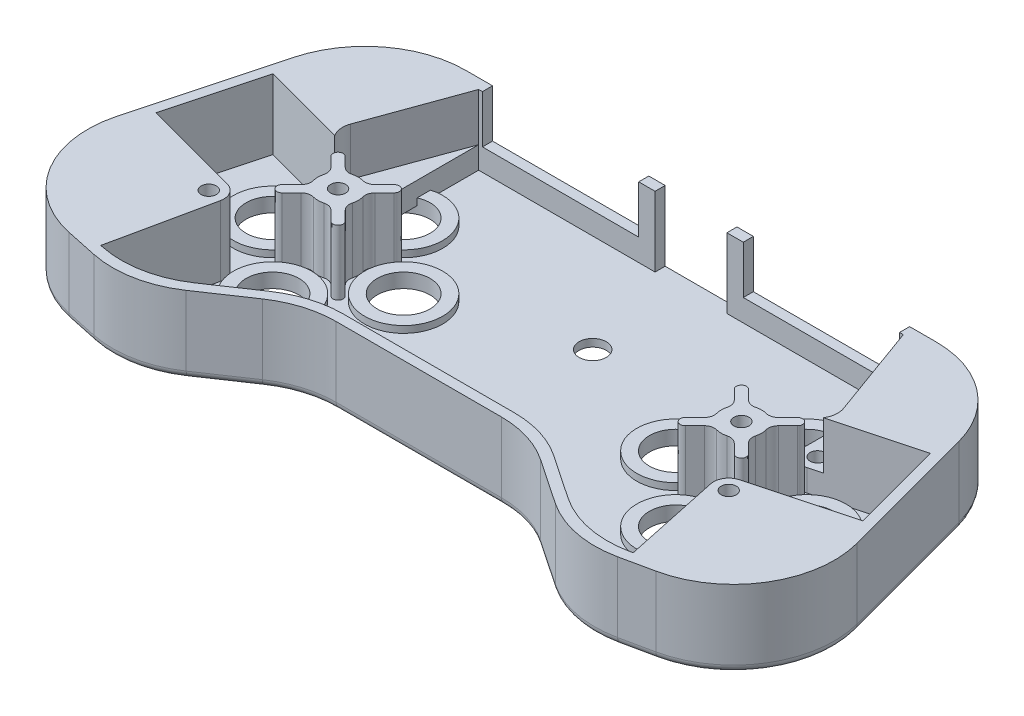
SolidWorks part; units mm, degrees
ref_plane "Front Plane" through (0, 0, 0) normal (0, 0, 1) x (1, 0, 0)
ref_plane "Top Plane" through (0, 0, 0) normal (0, 1, 0) x (1, 0, 0)
ref_plane "Right Plane" through (0, 0, 0) normal (1, 0, 0) x (0, 0, -1)
sketch "Sketch10" plane through (0, 0, 0) normal (0, 1, 0) x (1, 0, 0)
  line L0 (62, 32) -> (-62, 32)
  line L1 (-62, 32) -> (-78.8232, -30.7852)
  line L2 (-78.8232, -30.7852) -> (-43.6451, -38.2625)
  line L3 (-43.6451, -38.2625) -> (-22.5, -24)
  line L4 (-22.5, -24) -> (22.5, -24)
  line L5 (22.5, -24) -> (43.6451, -38.2625)
  line L6 (43.6451, -38.2625) -> (78.8232, -30.7852)
  line L7 (78.8232, -30.7852) -> (62, 32)
  line L8 (40, 13) -> (40, -13) construction
  line L9 (27, 0) -> (53, 0) construction
  line L10 (-40, 13) -> (-40, -13) construction
  line L11 (-53, 0) -> (-27, 0) construction
  line L12 (-27, 0) -> (27, 0) construction
  line L13 (0, 0) -> (0, 32) construction
  line L14 (0, 0) -> (0, -24) construction
  line L15 (78.8232, -30.7852) -> (22.5, -24) construction
  line L16 (-22.5, -24) -> (-78.8232, -30.7852) construction
  circle A0 centre (40, 13) radius 5.25
  circle A1 centre (27, 0) radius 5.25
  circle A2 centre (40, -13) radius 5.25
  circle A3 centre (53, 0) radius 5.25
  circle A4 centre (-40, 13) radius 5.25
  circle A5 centre (-53, 0) radius 5.25
  circle A6 centre (-40, -13) radius 5.25
  circle A7 centre (-27, 0) radius 5.25
  point P16 (40, 0)
  point P17 (-40, 0)
  dimension "D1" = 10.5
  dimension "D2" = 26
  dimension "D3" = 65
  dimension "D4" = 124
  dimension "D5" = 80
  dimension "D6" = 105
  dimension "D7" = 56
  dimension "D8" = 45
  dimension "D9" = 32
  dimension "D10" = 12
  dimension "D11" = 34
extrude "Boss-Extrude5" add sketch "Sketch10" along normal blind 1.5 separate body
sketch "Sketch11" plane through (0, 1.5, 0) normal (0, 1, 0) x (1, 0, 0)
  line L0 (-78.8232, -30.7852) -> (-62, 32)
  line L1 (-62, 32) -> (62, 32)
  line L2 (62, 32) -> (78.8232, -30.7852)
  line L3 (78.8232, -30.7852) -> (43.6451, -38.2625)
  line L4 (43.6451, -38.2625) -> (22.5, -24)
  line L5 (22.5, -24) -> (-22.5, -24)
  line L6 (-22.5, -24) -> (-43.6451, -38.2625)
  line L7 (-43.6451, -38.2625) -> (-78.8232, -30.7852)
  line L8 (-44.0596, -36.1297) -> (-76.3459, -29.2671)
  line L9 (-76.3459, -29.2671) -> (-60.4653, 30)
  line L10 (-60.4653, 30) -> (60.4653, 30)
  line L11 (60.4653, 30) -> (76.3459, -29.2671)
  line L12 (76.3459, -29.2671) -> (44.0596, -36.1297)
  line L13 (44.0596, -36.1297) -> (23.1115, -22)
  line L14 (23.1115, -22) -> (-23.1115, -22)
  line L15 (-23.1115, -22) -> (-44.0596, -36.1297)
  dimension "D1" = 2
extrude "Boss-Extrude7" add sketch "Sketch11" along direction (0, -1, 0) on the side of the normal offset from surface (13.875 mm away) 15.375 up to face at (-40, 0, 18.25)
fillet "Fillet4" radius 20 16 edges at (62, 7.6875, -32) (78.8232, 7.6875, 30.7852) (43.6451, 7.6875, 38.2625) (22.5, 7.6875, 24) (-22.5, 7.6875, 24) (-43.6451, 7.6875, 38.2625) (-62, 7.6875, -32) (-78.8232, 7.6875, 30.7852) (76.3459, 8.4375, 29.2671) (60.4653, 8.4375, -30) (44.0596, 8.4375, 36.1297) (23.1115, 8.4375, 22) (-23.1115, 8.4375, 22) (-44.0596, 8.4375, 36.1297) (-76.3459, 8.4375, 29.2671) (-60.4653, 8.4375, -30)
fillet "Fillet5" radius 1.5 16 edges at (43.9746, 0, 36.5671) (32.0881, 0, 30.4673) (22.2328, 0, 24.8739) (0, 0, 24) (-22.2328, 0, 24.8739) (-32.0881, 0, 30.4673) (-43.9746, 0, 36.5671) (-55.0786, 0, 35.8323) (-71.1028, 0, 26.0541) (-69.6702, 0, -3.3743) (-58.8287, 0, -27.8671) (0, 0, -32) (58.8287, 0, -27.8671) (69.6702, 0, -3.3743) (71.1028, 0, 26.0541) (55.0786, 0, 35.8323)
sketch "Sketch12" plane through (0, 1.5, 0) normal (0, 1, 0) x (1, 0, 0)
  line L0 (-65.2138, 12.2786) -> (-45.8953, 7.1022)
  line L1 (-64.4373, 15.1764) -> (-70.8911, -8.9096) construction
  line L2 (-42.1188, 10) -> (-42.1188, 30)
  line L3 (45.1188, 30) -> (-45.1188, 30) construction
  line L4 (-42.1188, 30) -> (-45.1188, 30)
  line L5 (-64.4373, 15.1764) -> (-65.2138, 12.2786)
  line L6 (-70.8911, -8.9096) -> (-70.1147, -6.0118)
  line L7 (-70.1147, -6.0118) -> (-50.7962, -11.1882)
  line L8 (-48.6382, -14.7097) -> (-52.7964, -34.2727)
  line L9 (-55.7309, -33.6489) -> (-52.3636, -34.3647) construction
  line L10 (-52.7964, -34.2727) -> (-55.7309, -33.6489)
  line L11 (0, 0) -> (0, 17.9434) construction
  line L12 (52.7964, -34.2727) -> (55.7309, -33.6489)
  line L13 (48.6382, -14.7097) -> (52.7964, -34.2727)
  line L14 (70.1147, -6.0118) -> (50.7962, -11.1882)
  line L15 (70.8911, -8.9096) -> (70.1147, -6.0118)
  line L16 (64.4373, 15.1764) -> (65.2138, 12.2786)
  line L17 (42.1188, 30) -> (45.1188, 30)
  line L18 (42.1188, 10) -> (42.1188, 30)
  line L19 (65.2138, 12.2786) -> (45.8953, 7.1022)
  arc A0 (-45.8953, 7.1022) -> (-42.1188, 10) centre (-45.1188, 10) ccw
  arc A1 (-45.1188, 30) -> (-64.4373, 15.1764) centre (-45.1188, 10) ccw
  arc A2 (-50.7962, -11.1882) -> (-48.6382, -14.7097) centre (-51.5726, -14.086) cw
  arc A3 (-55.7309, -33.6489) -> (-70.8911, -8.9096) centre (-51.5726, -14.086) cw
  circle A4 centre (-45.1188, 10) radius 1.5
  circle A5 centre (-51.5726, -14.086) radius 1.5
  circle A6 centre (51.5726, -14.086) radius 1.5
  circle A7 centre (45.1188, 10) radius 1.5
  arc A8 (55.7309, -33.6489) -> (70.8911, -8.9096) centre (51.5726, -14.086) ccw
  arc A9 (50.7962, -11.1882) -> (48.6382, -14.7097) centre (51.5726, -14.086) ccw
  arc A10 (45.1188, 30) -> (64.4373, 15.1764) centre (45.1188, 10) cw
  arc A11 (45.8953, 7.1022) -> (42.1188, 10) centre (45.1188, 10) cw
  point P45 (-51.5726, -14.086)
  point P46 (0, 0)
  point P47 (0, 0)
  point P48 (0, 0)
  dimension "D1" = 3
  dimension "D2" = 1.5
extrude "Boss-Extrude8" add sketch "Sketch12" along normal up to surface (13.875 mm away) up to face at (0, 15.375, 13.9064)
sketch "Sketch14" plane through (0, 0, -30) normal (0, 0, 1) x (1, 0, 0)
  line L0 (-42.1188, 15.375) -> (42.1188, 15.375) construction
  line L1 (-41.3688, 15.375) -> (-10.3688, 15.375)
  line L2 (-41.3688, 15.375) -> (-41.3688, 5.875)
  line L3 (-41.3688, 5.875) -> (-10.3688, 5.875)
  line L4 (-10.3688, 15.375) -> (-10.3688, 5.875)
  line L5 (0, 0) -> (0, 15.375) construction
  line L6 (10.3688, 15.375) -> (10.3688, 5.875)
  line L7 (41.3688, 5.875) -> (10.3688, 5.875)
  line L8 (41.3688, 15.375) -> (41.3688, 5.875)
  line L9 (41.3688, 15.375) -> (10.3688, 15.375)
  line L10 (-6.625, 14.53) -> (-6.625, 2) construction
  line L11 (-7.125, 15.375) -> (7.125, 15.375)
  line L12 (-7.125, 15.375) -> (-7.125, 1.5)
  line L13 (-7.125, 1.5) -> (7.125, 1.5)
  line L14 (7.125, 15.375) -> (7.125, 1.5)
  line L15 (42.1188, 1.5) -> (-42.1188, 1.5) construction
  dimension "D1" = 0.5
  dimension "D2" = 9.5
  dimension "D3" = 0.75
  dimension "D4" = 31
extrude "Cut-Extrude2" cut sketch "Sketch14" against normal through all
sketch "Sketch13" plane through (0, 15.375, 0) normal (0, 1, 0) x (1, 0, 0)
  line L0 (-48.879, 11.364) -> (-42.1188, 30)
  line L1 (-42.1188, 30) -> (-41.1238, 10.2008)
  line L2 (48.879, 11.364) -> (42.1188, 30)
  line L3 (42.1188, 30) -> (41.1238, 10.2008)
  arc A0 (-48.879, 11.364) -> (-41.1238, 10.2008) centre (-45.1188, 10) ccw
  arc A1 (41.1238, 10.2008) -> (48.879, 11.364) centre (45.1188, 10) ccw
  dimension "D1" = 8
extrude "Cut-Extrude1" cut sketch "Sketch13" against normal up to surface (9.5 mm away) up to face at (-25.8688, 5.875, -31)
sketch "Sketch15" plane through (0, 0, 0) normal (0, -1, 0) x (1, 0, 0)
  line L0 (0, -10.5) -> (0, -30.5) construction
  line L1 (-46.6535, -30.5) -> (46.6535, -30.5) construction
  circle A0 centre (0, -10.5) radius 2.7
  dimension "D2" = 5.4
  dimension "D1" = 20
extrude "Cut-Extrude3" cut sketch "Sketch15" against normal through all contours A0
sketch "Sketch16" plane through (0, 1.5, 0) normal (0, 1, 0) x (1, 0, 0)
  circle A0 centre (-40, 13) radius 7.75
  circle A1 centre (-40, 13) radius 5.25
  circle A2 centre (-27, 0) radius 7.75
  circle A3 centre (-27, 0) radius 5.25
  circle A4 centre (-53, 0) radius 5.25
  circle A5 centre (-53, 0) radius 7.75
  circle A6 centre (-40, -13) radius 5.25
  circle A7 centre (-40, -13) radius 7.75
  circle A8 centre (-40, 13) radius 5.25 construction
  circle A9 centre (-53, 0) radius 5.25 construction
  circle A10 centre (-40, -13) radius 5.25 construction
  circle A11 centre (-27, 0) radius 5.25 construction
  dimension "D1" = 2.5
extrude "Boss-Extrude9" add sketch "Sketch16" along normal blind 1.35
sketch "Sketch17" plane through (0, 1.5, 0) normal (0, 1, 0) x (1, 0, 0)
  line L0 (-43.4457, 2.0315) -> (-46.2741, 4.8599)
  line L3 (-44.8599, 6.2741) -> (-42.0315, 3.4457)
  line L4 (-37.9685, 3.4457) -> (-35.1401, 6.2741)
  line L5 (-33.7259, 4.8599) -> (-36.5543, 2.0315)
  line L6 (-36.5543, -2.0315) -> (-33.7259, -4.8599)
  line L7 (-35.1401, -6.2741) -> (-37.9685, -3.4457)
  line L8 (-42.0315, -3.4457) -> (-44.8599, -6.2741)
  line L9 (-46.2741, -4.8599) -> (-43.4457, -2.0315)
  line L10 (-45.567, -5.567) -> (-40, 0) construction
  line L11 (-40, 0) -> (-34.433, 5.567) construction
  line L12 (-34.433, -5.567) -> (-40, 0) construction
  line L13 (-45.567, 5.567) -> (-40, 0) construction
  line L14 (-45.567, 5.567) -> (-34.433, 5.567) construction
  line L15 (-40, 0) -> (0, 0) construction
  arc A0 (-43.4457, 2.0315) -> (-43.4457, -2.0315) centre (-40, 0) ccw
  arc A3 (-46.2741, 4.8599) -> (-44.8599, 6.2741) centre (-45.567, 5.567) cw
  arc A4 (-35.1401, 6.2741) -> (-33.7259, 4.8599) centre (-34.433, 5.567) cw
  arc A5 (-33.7259, -4.8599) -> (-35.1401, -6.2741) centre (-34.433, -5.567) cw
  arc A6 (-44.8599, -6.2741) -> (-46.2741, -4.8599) centre (-45.567, -5.567) cw
  arc A7 (-37.9685, 3.4457) -> (-42.0315, 3.4457) centre (-40, 0) ccw
  arc A8 (-36.5543, -2.0315) -> (-36.5543, 2.0315) centre (-40, 0) ccw
  arc A9 (-42.0315, -3.4457) -> (-37.9685, -3.4457) centre (-40, 0) ccw
  circle A10 centre (-40, 0) radius 1.5
  dimension "D1" = 40
  dimension "D4" = 8
  dimension "D5" = 3
  dimension "D2" = 2
  dimension "D3" = 4
extrude "Boss-Extrude10" add sketch "Sketch17" along normal offset from surface (12.875 mm away) 1 up to face at (-51.5726, 15.375, 12.586)
fillet "Fillet6" radius 2 8 edges at (-43.4457, 7.9375, 2.0315) (-43.4457, 7.9375, -2.0315) (-42.0315, 7.9375, -3.4457) (-37.9685, 7.9375, -3.4457) (-36.5543, 7.9375, -2.0315) (-36.5543, 7.9375, 2.0315) (-37.9685, 7.9375, 3.4457) (-42.0315, 7.9375, 3.4457)
mirror "Mirror1" about plane through (0, 0, 0) normal (1, 0, 0) of "Fillet6", "Boss-Extrude9", "Boss-Extrude10"
